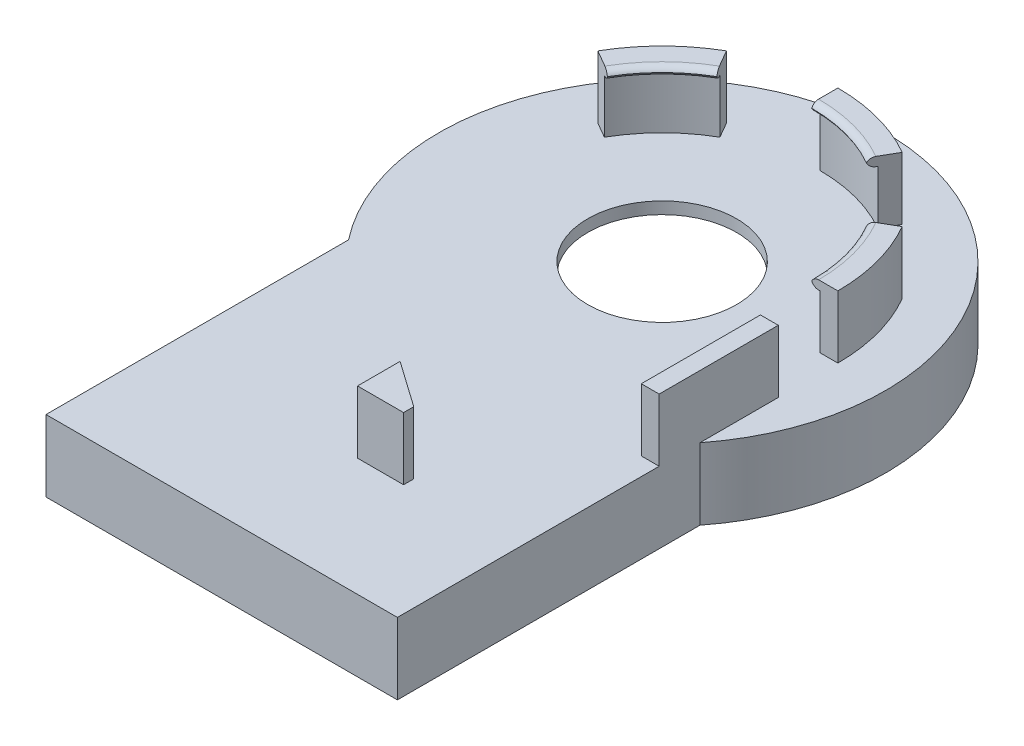
SolidWorks part; units mm, degrees
ref_plane "Front Plane" through (0, 0, 0) normal (0, 0, 1) x (1, 0, 0)
ref_plane "Top Plane" through (0, 0, 0) normal (0, 1, 0) x (1, 0, 0)
ref_plane "Right Plane" through (0, 0, 0) normal (1, 0, 0) x (0, 0, -1)
sketch "Sketch1" plane through (0, 0, 0) normal (0, 1, 0) x (1, 0, 0)
  circle A0 centre (0, 0) radius 35.5
  circle A1 centre (0, 0) radius 37.5
  dimension "D1" = 71
  dimension "D2" = 2
extrude "Boss-Extrude1" add sketch "Sketch1" along normal blind 10
sketch "Sketch2" plane through (0, 10, 0) normal (0, 1, 0) x (1, 0, 0)
  circle A0 centre (0, 0) radius 37.5
  circle A1 centre (0, 0) radius 12.5
  dimension "D1" = 75
  dimension "D2" = 25
extrude "Boss-Extrude2" add sketch "Sketch2" along normal blind 2
sketch "Sketch4" plane through (0, 12, 0) normal (0, 1, 0) x (1, 0, 0)
  line L0 (0, 26.5) -> (0, 29.5)
  line L1 (-13.25, 22.9497) -> (-14.75, 25.5477)
  line L2 (13.25, 22.9497) -> (14.75, 25.5477)
  line L3 (22.9497, 13.25) -> (25.5477, 14.75)
  line L4 (26.5, 0) -> (29.5, 0)
  line L5 (29.5, 0) -> (26.5, 0)
  line L6 (-22.9497, 13.25) -> (-25.5477, 14.75)
  arc A0 (-13.25, 22.9497) -> (-22.9497, 13.25) centre (0, 0) ccw
  arc A1 (-14.75, 25.5477) -> (-25.5477, 14.75) centre (0, 0) ccw
  arc A2 (13.25, 22.9497) -> (0, 26.5) centre (0, 0) ccw
  arc A3 (14.75, 25.5477) -> (0, 29.5) centre (0, 0) ccw
  arc A4 (29.5, 0) -> (25.5477, 14.75) centre (0, 0) ccw
  arc A5 (26.5, 0) -> (22.9497, 13.25) centre (0, 0) ccw
  dimension "D2" = 3
  dimension "D3" = 30
  dimension "D4" = 30
  dimension "D5" = 30
  dimension "D6" = 30
  dimension "D7" = 30
extrude "Boss-Extrude3" add sketch "Sketch4" along normal blind 9 contours L2 A3 L0 A2 | A5 L4 A4 L3 | L1 A1 L6 A0 region at (7.1713, 12, -26.7636) region at (-19.5923, 12, -19.5923) region at (26.7636, 12, -7.1713)
sketch "Sketch5" plane through (0, 21, 0) normal (0, 1, 0) x (1, 0, 0)
  line L0 (-14.75, 25.5477) -> (-12.5, 21.6506)
  line L1 (-25.5477, 14.75) -> (-21.6506, 12.5)
  line L2 (0, 29.5) -> (0, 25)
  line L3 (14.75, 25.5477) -> (12.4211, 21.514)
  line L4 (25.5477, 14.75) -> (21.6506, 12.5)
  line L5 (29.5, 0) -> (24.8232, 0)
  circle A0 centre (0, 0) radius 29.5
  circle A1 centre (0, 0) radius 25
  line M2 (13.25, 22.9497) -> (14.75, 25.5477)
  arc M3 (14.75, 25.5477) -> (0, 29.5) centre (0, 0) ccw
  line M4 (0, 29.5) -> (0, 26.5)
  arc M5 (0, 26.5) -> (13.25, 22.9497) centre (0, 0) cw
  dimension "D1" = 59
  dimension "D2" = 4.5
extrude "Boss-Extrude4" add sketch "Sketch5" along normal blind 1.5 contours A1 L0 A0 L1 | M5 M2 M3 M4 | A1 L3 L2 M5 | A1 L5 A0 L4 region at (-19.0926, 21, -19.0926) region at (7.1713, 21, -26.7636) region at (6.5906, 21, -24.5964) region at (26.081, 21, -6.9884)
fillet "Fillet1" radius 1.27 6 edges at (24.1481, 21, -6.4705) (24.1481, 22.5, -6.4705) (6.4705, 21, -24.1481) (6.4705, 22.5, -24.1481) (-17.6777, 21, -17.6777) (-17.6777, 22.5, -17.6777)
sketch "Sketch6" plane through (0, 0, 0) normal (0, 0, 1) x (1, 0, 0)
  line L1 (29.5, 22.5) -> (26.5, 22.5)
  line L2 (29.5, 22.5) -> (29.5, 12)
  line L3 (29.5, 12) -> (26.5, 12)
  line L4 (26.5, 22.5) -> (26.5, 12)
extrude "Boss-Extrude5" add sketch "Sketch6" along normal blind 30
sketch "Sketch7" plane through (0, 22.5, 0) normal (0, 1, 0) x (1, 0, 0)
  line L0 (29.5, -30) -> (29.5, 0) construction
  line L1 (26.5, 0) -> (29.5, 0)
  line L2 (26.5, 0) -> (26.5, -10)
  line L3 (26.5, -10) -> (29.5, -10)
  line L4 (29.5, 0) -> (29.5, -10)
  point P7 (28, -10)
  dimension "D1" = 10
extrude "Cut-Extrude1" cut sketch "Sketch7" against normal blind 10.5
sketch "Sketch8" plane through (0, 12, 0) normal (0, 1, 0) x (1, 0, 0)
  line L1 (10.7332, -52.4415) -> (3, -47)
  line L2 (10.7332, -52.4415) -> (10.7332, -54.1483)
  line L3 (10.7332, -54.1483) -> (3, -54.1483)
  line L4 (3, -47) -> (3, -54.1483)
  dimension "D1" = 47
  dimension "D2" = 3
extrude "Boss-Extrude6" add sketch "Sketch8" along normal blind 10.5 separate body
sketch "Sketch9" plane through (0, 12, 0) normal (0, 1, 0) x (1, 0, 0)
  line L0 (-26.9119, -23.1517) -> (-29.5, -23.1517)
  line L1 (29.5, -23.1517) -> (26.9119, -23.1517)
  line L2 (29.5, -23.1517) -> (29.5, -73.9517)
  line L3 (29.5, -73.9517) -> (-29.5, -73.9517)
  line L4 (-29.5, -23.1517) -> (-29.5, -73.9517)
  arc A0 (29.5, -23.1517) -> (26.5, -26.533) centre (0, 0) ccw construction
  arc A1 (-26.9119, -23.1517) -> (26.9119, -23.1517) centre (0, 0) ccw
  dimension "D1" = 2
  dimension "D2" = 50.8
extrude "Boss-Extrude8" add sketch "Sketch9" against normal up to surface (12 mm away) contours L4 L3 L2 L1 A1 L0 up to face at (0, 0, 37.5)
